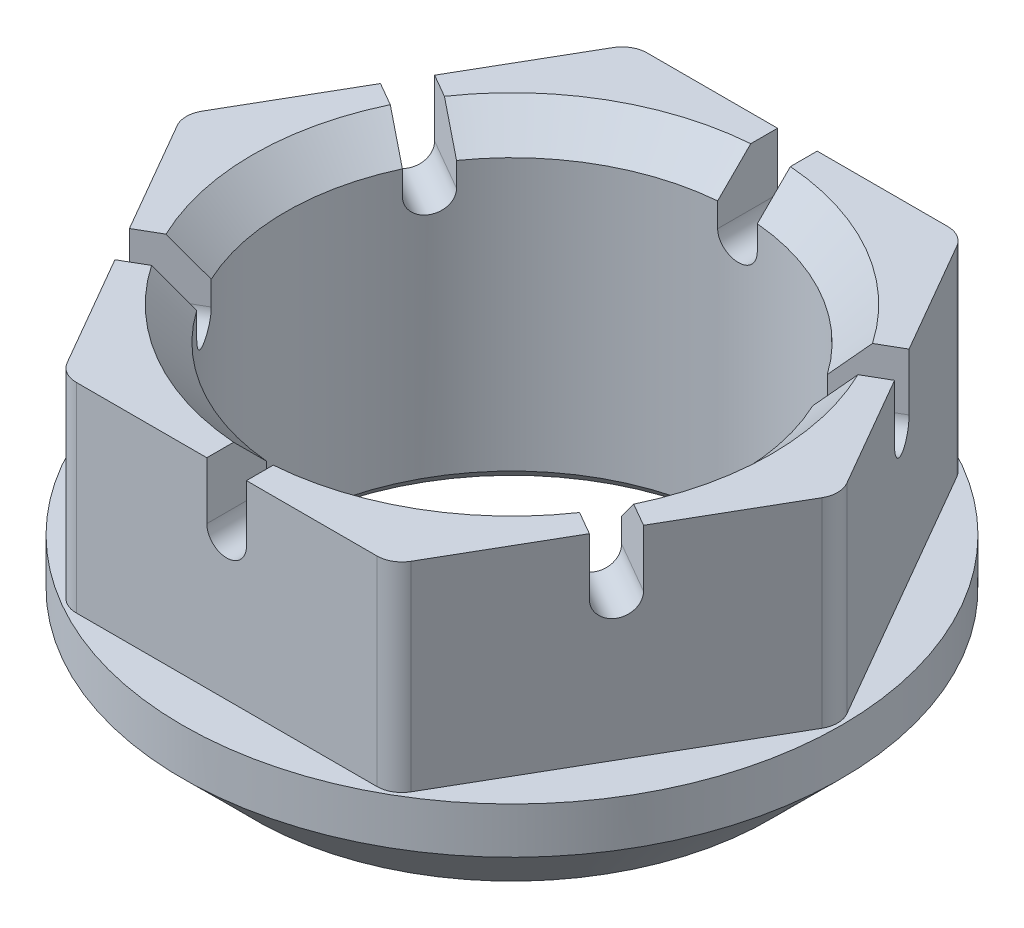
SolidWorks part; units mm, degrees
note: '?' marks a value the reader was unsure of.
material "6061-T6 (SS)"
ref_plane "X-Y Datum" through (0, 0, 0) normal (0, 0, 1) x (1, 0, 0)
ref_plane "X-Z Datum" through (0, 0, 0) normal (0, 1, 0) x (1, 0, 0)
ref_plane "Y-Z Datum" through (0, 0, 0) normal (1, 0, 0) x (0, 0, -1)
sketch "Sketch1" plane through (0, 0, 0) normal (1, 0, 0) x (0, 0, -1)
  line L0 (0, 0) -> (0, 50000) construction
  line L1 (0, 0) -> (-50000, 0) construction
  line L2 (-22.6695, -31.75) -> (-22.6695, 0)
  line L3 (-22.6695, 0) -> (-33, 0)
  line L4 (-33, 0) -> (-33, -24.6194)
  line L6 (-33, -24.6194) -> (-25.8445, -31.75)
  line L7 (-25.8445, -31.75) -> (-22.6695, -31.75)
  dimension "D1" = 66
  dimension "D2" = 3.175
  dimension "D3" = 31.75
  dimension "D4" = 45.339
  dimension "D5" = 45.1
  dimension "D6" = 24.6194
revolve "Revolve1" add sketch "Sketch1" angle 360 about L0
ref_axis "Axis1" through (0, 2.4756, 0) along (0, -1, 0)?
thread "Thread1" [suppressed] pitch 2.1167 start angle 0, offset 0, length 0, pitch 2.1167, diameter 45.339
ref_plane "Plane1" through (22.6695, -31.75, 0) normal (0, 0, 1) x (1, 0, 0)
sketch "Thread Profile1" plane through (22.6695, -31.75, 0) normal (0, 0, 1) x (1, 0, 0)
  line L0 (0, 0) -> (0, 2.1167) construction
  line L1 (0, 0) -> (1.1457, 0.6615)
  line L2 (1.1457, 0.6615) -> (1.1457, 0.926)
  line L3 (1.1457, 0.926) -> (0, 1.5875)
  line L4 (1.1457, 0.7937) -> (0, 0.7937) construction
  line L11 (0, 0) -> (0, 1.5875)
  point P2 (0, 0)
  dimension "Pitch" = 2.1167
  dimension "Profile_Angle" = 60
  dimension "Profile_Land" = 0.2646
  dimension "Profile_Height" = 1.1457
sketch "Sketch4" plane through (0, 0, 0) normal (0, 1, 0) x (1, 0, 0)
  line L1 (16.5, 28.5788) -> (-16.5, 28.5788)
  line L2 (-16.5, 28.5788) -> (-33, 0)
  line L3 (-33, 0) -> (-16.5, -28.5788)
  line L4 (-16.5, -28.5788) -> (16.5, -28.5788)
  line L5 (16.5, -28.5788) -> (33, 0)
  line L6 (33, 0) -> (16.5, 28.5788)
  circle A0 centre (0, 0) radius 28.5788 construction
  circle A1 centre (0, 0) radius 33 construction
  circle A2 centre (0, 0) radius 33 construction
  point P14 (0, 28.5788)
  circle M16 centre (0, 0) radius 33
extrude "Cut-Extrude5" cut sketch "Sketch4" against normal blind 20 contours L6 L5 L4 L3 L2 L1 M16 | L1 M16 | L2 M16 | L3 M16 | L4 M16 | L5 M16
fillet "Fillet4" radius 2.5 6 edges at (16.5, -10, 28.5788) (33, -10, 0) (16.5, -10, -28.5788) (-16.5, -10, -28.5788) (-33, -10, 0) (-16.5, -10, 28.5788)
sketch "Sketch7" plane through (0, 0, 0) normal (0, 0, 1) x (1, 0, 0)
  line L0 (0, 0) -> (1.9844, 0)
  line L1 (1.9844, 0) -> (1.9844, -5.715)
  line L2 (-1.9844, 0) -> (-1.9844, -5.715)
  line L3 (0, 0) -> (1.9844, 0)
  line L4 (0, 0) -> (-1.9844, 0)
  arc A2 (-1.9844, -5.715) -> (1.9844, -5.715) centre (0, -5.715) ccw
  dimension "D1" = 5.715
  dimension "D2" = 3.9688
extrude "Cut-Extrude6" cut sketch "Sketch7" along normal through all both and the other way through all from surface at -28.5788 contours L2 A2 L1 L0 L4 starting at face at (0, -10, -28.5788)
pattern_circular "CirPattern2" count 6 over 360 about axis through (0, 0, 0) along (0, 1, 0) of "Cut-Extrude6"
chamfer "Chamfer1" distance 3.302 angle 45 6 edges at (-11.3348, 0, 19.6324) (-22.6695, 0, 0) (11.3348, 0, 19.6324) (22.6695, 0, 0) (11.3347, 0, -19.6324) (-11.3348, 0, -19.6324)
chamfer "Chamfer2" distance 1.27 angle 45 1 edges at (0, -31.75, -22.6695)
